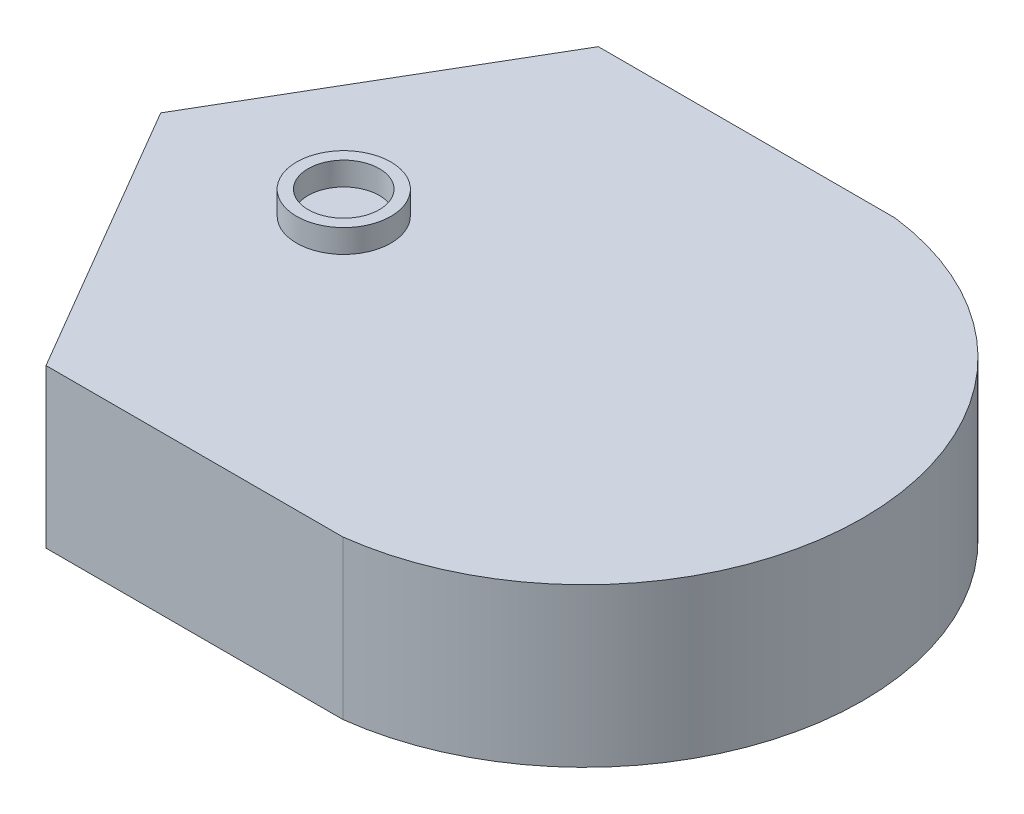
SolidWorks part; units mm, degrees
ref_plane "Front Plane" through (0, 0, 0) normal (0, 0, 1) x (1, 0, 0)
ref_plane "Top Plane" through (0, 0, 0) normal (0, 1, 0) x (1, 0, 0)
ref_plane "Right Plane" through (0, 0, 0) normal (1, 0, 0) x (0, 0, -1)
sketch "Sketch2" plane through (0, 0, 0) normal (0, 1, 0) x (1, 0, 0)
  line L1 (-14.4231, 13.5577) -> (34.5769, 13.5577)
  line L2 (-14.4231, 13.5577) -> (-14.4231, -6.4423)
  line L3 (-14.4231, -6.4423) -> (34.5769, -6.4423)
  line L4 (34.5769, 13.5577) -> (34.5769, -6.4423)
  dimension "D1" = 49
  dimension "D2" = 20
extrude "Boss-Extrude1" add sketch "Sketch2" along normal blind 10
sketch "Sketch3" plane through (0, 0, 0) normal (0, -1, 0) x (1, 0, 0)
  line L0 (34.5769, 6.4423) -> (34.5769, -13.5577) construction
  line L1 (27.5769, -5.0677) -> (-2.4231, -5.0677)
  line L2 (27.5769, -5.0677) -> (27.5769, -2.0477)
  line L3 (27.5769, -2.0477) -> (-2.4231, -2.0477)
  line L4 (-2.4231, -5.0677) -> (-2.4231, -2.0477)
  line L5 (-14.4231, -3.5577) -> (34.5769, -3.5577) construction
  line L6 (-14.4231, -13.5577) -> (-14.4231, 6.4423) construction
  dimension "D1" = 30
  dimension "D2" = 7
  dimension "D3" = 3.02
  dimension "D4" = 1.51
extrude "Cut-Extrude1" cut sketch "Sketch3" against normal blind 2
sketch "Sketch4" plane through (0, 0, 0) normal (0, -1, 0) x (1, 0, 0)
  line L0 (-2.4231, -2.0477) -> (-2.4231, -5.0677) construction
  line L1 (-2.4231, -6.5477) -> (-7.4231, -6.5477)
  line L2 (-2.4231, -6.5477) -> (-2.4231, -0.5477)
  line L3 (-2.4231, -0.5477) -> (-7.4231, -0.5477)
  line L4 (-7.4231, -6.5477) -> (-7.4231, -0.5477)
  line L6 (27.5769, -2.0477) -> (-2.4231, -2.0477) construction
  dimension "D1" = 6
  dimension "D2" = 5
  dimension "D3" = 1.5
extrude "Cut-Extrude2" cut sketch "Sketch4" against normal blind 5
sketch "Sketch5" plane through (0, 5, 0) normal (0, -1, 0) x (1, 0, 0)
  line L0 (-7.4231, -3.5477) -> (-2.4231, -3.5577) construction
  line L1 (-7.4231, -0.5477) -> (-7.4231, -6.5477) construction
  line L2 (-2.4231, -2.0477) -> (-2.4231, -5.0677) construction
  circle A0 centre (-4.9231, -3.5527) radius 7
  dimension "D1" = 14
extrude "Cut-Extrude3" cut sketch "Sketch5" against normal through all
sketch "Sketch12" plane through (0, 0, 0) normal (0, -1, 0) x (1, 0, 0)
  line L1 (-7.4231, -0.5477) -> (-2.4231, -0.5477)
  line L2 (-7.4231, -0.5477) -> (-7.4231, -6.5477)
  line L3 (-7.4231, -6.5477) -> (-2.4231, -6.5477)
  line L4 (-2.4231, -0.5477) -> (-2.4231, -6.5477)
extrude "Boss-Extrude4" add sketch "Sketch12" against normal blind 0.8
sketch "Sketch14" plane through (0, 0, 6.4423) normal (0, 0, 1) x (1, 0, 0)
  line L0 (-14.4231, 10) -> (34.5769, 10) construction
  line L1 (5.0769, 10) -> (34.5769, 10)
  line L2 (5.0769, 10) -> (5.0769, 4)
  line L3 (5.0769, 4) -> (34.5769, 4)
  line L4 (34.5769, 10) -> (34.5769, 4)
  line L5 (34.5769, 10) -> (34.5769, 0) construction
  line L6 (27.5769, 2) -> (-2.4231, 2) construction
  line L7 (2.0769, 5) -> (2.0769, 10) construction
  dimension "D1" = 2
  dimension "D2" = 3
extrude "Cut-Extrude6" cut sketch "Sketch14" against normal through all
sketch "Sketch20" plane through (0, 0.8, 0) normal (0, 1, 0) x (1, 0, 0)
  line L0 (-2.4231, 0.5477) -> (-7.4231, 0.5477) construction
  line L1 (-7.4231, 6.5477) -> (-2.4231, 6.5477)
  line L2 (-7.4231, 6.5477) -> (-7.4231, 0.5477)
  line L3 (-7.4231, 0.5477) -> (-2.4231, 0.5477)
  line L4 (-2.4231, 6.5477) -> (-2.4231, 0.5477)
  line L5 (-2.4231, 0.5477) -> (-7.4231, 0.5477) construction
extrude "Boss-Extrude6" add sketch "Sketch20" along normal up to surface (4.2 mm away) up to face at (-4.9231, 5, -10.5527)
sketch "Sketch21" plane through (0, 5, 0) normal (0, 1, 0) x (1, 0, 0)
  circle A0 centre (-4.9231, 3.5527) radius 4.6
  dimension "D1" = 9.2
extrude "Cut-Extrude8" cut sketch "Sketch21" against normal blind 0.5
sketch "Sketch22" plane through (0, 4.5, 0) normal (0, 1, 0) x (1, 0, 0)
  circle A0 centre (-4.9231, 3.5527) radius 3.825
  dimension "D1" = 7.65
extrude "Cut-Extrude9" cut sketch "Sketch22" against normal blind 4
sketch "Sketch24" plane through (0, 5, 0) normal (0, 1, 0) x (1, 0, 0)
  circle A0 centre (-4.9231, 3.5527) radius 4.25
  circle A1 centre (-4.9231, 3.5527) radius 4.6
  dimension "D1" = 9.2
  dimension "D2" = 8.5
extrude "Cut-Extrude11" cut sketch "Sketch24" against normal blind 1
sketch "Sketch26" plane through (0, 4.5, 0) normal (0, 1, 0) x (1, 0, 0)
  circle A0 centre (-4.9231, 3.5527) radius 3.825
  circle A1 centre (-4.9231, 3.5527) radius 5.0656
extrude "Boss-Extrude9" add sketch "Sketch26" along normal blind 8
sketch "Sketch27" plane through (0, 5, 0) normal (0, 1, 0) x (1, 0, 0)
  circle A0 centre (-4.9231, 3.5527) radius 4.6
  circle A1 centre (-4.9231, 3.5527) radius 7
extrude "Cut-Extrude12" cut sketch "Sketch27" against normal blind 1
sketch "Sketch39" plane through (0, 4, 0) normal (0, 1, 0) x (1, 0, 0)
  line L0 (5.0769, 3.5577) -> (29.0295, 3.5577) construction
  line L1 (5.0769, 13.5577) -> (5.0769, -6.4423) construction
  line L4 (6.3269, -0.6923) -> (6.3269, 8.9673) construction
  line L5 (5.0769, 13.5577) -> (5.0769, -6.4423) construction
  circle A0 centre (6.3269, -0.6923) radius 0.6
  circle A1 centre (7.5769, 7.8077) radius 0.6
  circle A2 centre (9.9936, 7.8077) radius 0.6
  circle A3 centre (8.7436, -0.6923) radius 0.6
  circle A4 centre (12.4103, 7.8077) radius 0.6
  circle A5 centre (11.1603, -0.6923) radius 0.6
  circle A6 centre (14.8269, 7.8077) radius 0.6
  circle A7 centre (13.5769, -0.6923) radius 0.6
  circle A8 centre (17.2436, 7.8077) radius 0.6
  circle A9 centre (15.9936, -0.6923) radius 0.6
  circle A10 centre (19.6603, 7.8077) radius 0.6
  circle A11 centre (18.4103, -0.6923) radius 0.6
  circle A12 centre (22.0769, 7.8077) radius 0.6
  circle A13 centre (20.8269, -0.6923) radius 0.6
  circle A22 centre (24.4936, 7.8077) radius 0.6 [skipped]
  circle A23 centre (23.2436, -0.6923) radius 0.6 [skipped]
  dimension "D1" = 1.2
  dimension "D2" = 1.2
  dimension "D7" = 1.25
  dimension "D3" = 8.5
  dimension "D4" = 1.25
  dimension "D5" = 4.25
  dimension "D6" = 8
fillet "Fillet1" radius 0.5 1 edges at (5.0769, 4, -3.5577)
sketch "Sketch56" plane through (0, 0, 0) normal (0, -1, 0) x (1, 0, 0)
  line L0 (27.5769, -2.0477) -> (-2.4231, -2.0477) construction
  line L1 (-2.4231, -5.0677) -> (-2.4231, -2.0477) construction
  circle A0 centre (28.9269, -3.5577) radius 2
  dimension "D1" = 4
  dimension "D2" = 1.51
  dimension "D3" = 31.35
extrude "Cut-Extrude13" cut sketch "Sketch56" against normal up to surface (2 mm away) up to face at (13.1618, 2, -3.5578)
sketch "Sketch57" plane through (0, 4, 0) normal (0, 1, 0) x (1, 0, 0)
  line L0 (26.0569, 11.0577) -> (26.0569, -3.9423) construction
  line L1 (24.4319, 0.5577) -> (21.4319, 0.5577)
  line L2 (30.6819, 0.5577) -> (27.6819, 0.5577)
  line L3 (30.6819, 0.5577) -> (30.6819, 6.5577)
  line L4 (30.6819, 6.5577) -> (27.6819, 6.5577)
  line L5 (27.6819, 0.5577) -> (27.6819, 6.5577)
  line L6 (30.6819, 0.5577) -> (27.6819, 6.5577) construction
  line L7 (30.6819, 6.5577) -> (27.6819, 0.5577) construction
  line L8 (24.4319, 0.5577) -> (24.4319, 6.5577)
  line L9 (24.4319, 6.5577) -> (21.4319, 6.5577)
  line L10 (21.4319, 0.5577) -> (21.4319, 6.5577)
  line L11 (24.4319, 0.5577) -> (21.4319, 6.5577) construction
  line L12 (24.4319, 6.5577) -> (21.4319, 0.5577) construction
  line L13 (5.5769, 13.5577) -> (5.5769, -6.4423) construction
  line L14 (5.5769, 13.5577) -> (34.5769, 13.5577) construction
  circle A1 centre (26.0569, 3.5577) radius 6
  circle A2 centre (26.0569, 3.5577) radius 5.8
  point P6 (26.0569, 3.5577)
  point P7 (29.1819, 3.5577)
  point P19 (22.9319, 3.5577)
  dimension "D1" = 11.6
  dimension "D2" = 0.2
  dimension "D3" = 15
  dimension "D4" = 3
  dimension "D11" = 20.48
  dimension "D5" = 6
  dimension "D6" = 3.125
  dimension "D7" = 3.125
  dimension "D8" = 6
  dimension "D9" = 3
  dimension "D10" = 20.48
  dimension "D12" = 10
extrude "Boss-Extrude19" add sketch "Sketch57" along normal blind 5.3 contours L5 L2 L3 L4 | L10 L1 L8 L9 region at (22.9319, 4, -3.5577) region at (29.1819, 4, -3.5577)
sketch "Sketch58" plane through (30.6819, 0, 0) normal (1, 0, 0) x (0, 0, -1)
  line L2 (0.5577, 4) -> (6.5577, 4) construction
  line L3 (0.5577, 9.3) -> (0.5577, 4) construction
  circle A0 centre (3.5577, 7) radius 1.5
  dimension "D1" = 3
  dimension "D2" = 3
  dimension "D3" = 3
extrude "Cut-Extrude14" cut sketch "Sketch58" against normal up to surface (9.25 mm away) up to face at (21.4319, 6.65, -3.5577)
fillet "Fillet2" radius 0.3 2 edges at (24.4319, 9.3, -3.5577) (27.6819, 9.3, -3.5577)
fillet "Fillet3" radius 0.8 10 edges at (21.4319, 6.65, -0.5577) (21.4319, 6.65, -6.5577) (21.4319, 4, -3.5577) (22.9319, 4, -6.5577) (30.6819, 6.65, -6.5577) (29.1819, 4, -6.5577) (30.6819, 6.65, -0.5577) (30.6819, 4, -3.5577) (29.1819, 4, -0.5577) (22.9319, 4, -0.5577)
ref_plane "Plane1" through (0, 0, -3.5577) normal (0, 0, -1) x (-1, 0, 0)
sketch "Sketch60" plane through (0, 0, -13.5577) normal (0, 0, -1) x (-1, 0, 0)
  line L1 (-34.5769, 4) -> (-15.5769, 4)
  line L2 (-34.5769, 4) -> (-34.5769, 0)
  line L3 (-34.5769, 0) -> (-15.5769, 0)
  line L4 (-15.5769, 4) -> (-15.5769, 0)
  line L5 (-34.5769, 0) -> (14.4231, 0) construction
  dimension "D1" = 19
extrude "Boss-Extrude21" add sketch "Sketch60" along normal blind 1
sketch "Sketch59" plane through (0, 0, -14.5577) normal (0, 0, -1) x (-1, 0, 0)
  line L0 (-15.5769, 0) -> (14.4231, 0) construction
  line L1 (-38.3869, -3) -> (-15.5269, -3)
  line L2 (-38.3869, -3) -> (-38.3869, 10)
  line L3 (-38.3869, 10) -> (-15.5269, 10)
  line L4 (-15.5269, -3) -> (-15.5269, 10)
  line L5 (-34.5769, 4) -> (-34.5769, 0) construction
  dimension "D1" = 22.86
  dimension "D2" = 13
  dimension "D3" = 3
  dimension "D4" = 3.81
extrude "Boss-Extrude20" add sketch "Sketch59" along normal blind 11
ref_axis "Axis1" through (28.9269, 2, -3.5577) along (0, -1, 0)
mirror "Mirror4" about plane through (0, 0, -3.5577) normal (0, 0, -1) of "Boss-Extrude20", "Boss-Extrude21"
sketch "Sketch61" plane through (0, 10, 0) normal (0, 1, 0) x (1, 0, 0)
  line L0 (24.4319, 7.3577) -> (24.4319, 20.2077) construction
  line L1 (-14.4231, 3.5577) -> (34.5769, 3.5577) construction
  line L2 (-14.4231, 13.5577) -> (-14.4231, -6.4423) construction
  line L3 (34.5769, 14.5577) -> (34.5769, -7.4423) construction
  line L4 (24.4319, 20.2077) -> (20.4069, 20.2077) construction
  line L5 (27.6819, 7.3577) -> (27.6819, 20.2077) construction
  line L6 (27.6819, 20.2077) -> (31.7069, 20.2077) construction
  line L7 (27.6819, -13.0923) -> (31.7069, -13.0923) construction
  line L8 (27.6819, -0.2423) -> (27.6819, -13.0923) construction
  line L9 (24.4319, -13.0923) -> (20.4069, -13.0923) construction
  line L10 (24.4319, -0.2423) -> (24.4319, -13.0923) construction
  circle A0 centre (20.4069, 20.2077) radius 2.5
  circle A1 centre (31.7069, 20.2077) radius 2.5
  circle A2 centre (31.7069, -13.0923) radius 2.5
  circle A3 centre (20.4069, -13.0923) radius 2.5
  dimension "D3" = 5
  dimension "D2" = 11.3
  dimension "D4" = 16.65
extrude "Cut-Extrude15" cut sketch "Sketch61" against normal up to next
fillet "Fillet4" radius 4 8 edges at (38.3869, 3.5, -25.5577) (15.5269, 3.5, -25.5577) (38.3869, 3.5, -14.5577) (38.3869, 3.5, 7.4423) (38.3869, 3.5, 18.4423) (15.5269, 3.5, 18.4423) (-14.4231, 5, 6.4423) (-14.4231, 5, -13.5577)
sketch "Sketch62" plane through (0, 10, 0) normal (0, 1, 0) x (1, 0, 0)
  line L4 (-24.3617, 3.3145) -> (-7.0052, -26.3726)
  line L5 (-7.0052, -26.3726) -> (24.8997, -26.3726)
  line L6 (-24.3617, 3.3145) -> (-7.0052, 33.0017)
  line L7 (-7.0052, 33.0017) -> (24.8997, 33.0017)
  arc A1 (24.8997, 33.0017) -> (24.8997, -26.3726) centre (21.1852, 3.3145) cw
  point P0 (0, 0)
  point P10 (0, 0)
  point P14 (51.1038, 3.3145)
  point P15 (-5.0074, -26.2671)
  point P16 (0, 0)
extrude "Boss-Extrude22" add sketch "Sketch62" against normal blind 17
